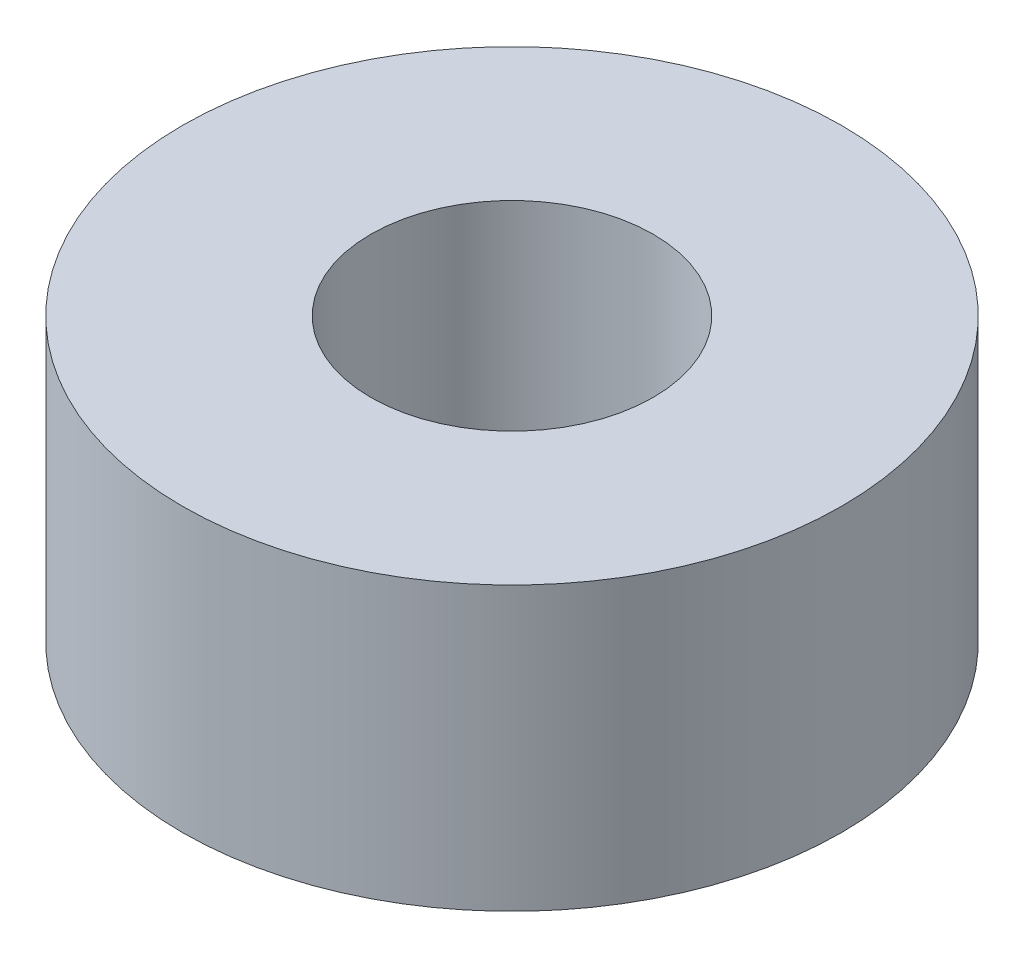
SolidWorks part; units mm, degrees
ref_plane "Front Plane" through (0, 0, 0) normal (0, 0, 1) x (1, 0, 0)
ref_plane "Top Plane" through (0, 0, 0) normal (0, 1, 0) x (1, 0, 0)
ref_plane "Right Plane" through (0, 0, 0) normal (1, 0, 0) x (0, 0, -1)
sketch "Sketch1" plane through (0, 0, 0) normal (0, 1, 0) x (1, 0, 0)
  circle A0 centre (0, 0) radius 1.5
  circle A1 centre (0, 0) radius 3.5
  dimension "D1" = 3
  dimension "D2" = 7
extrude "Boss-Extrude1" add sketch "Sketch1" along normal blind 1.5 and the other way blind 1.5
